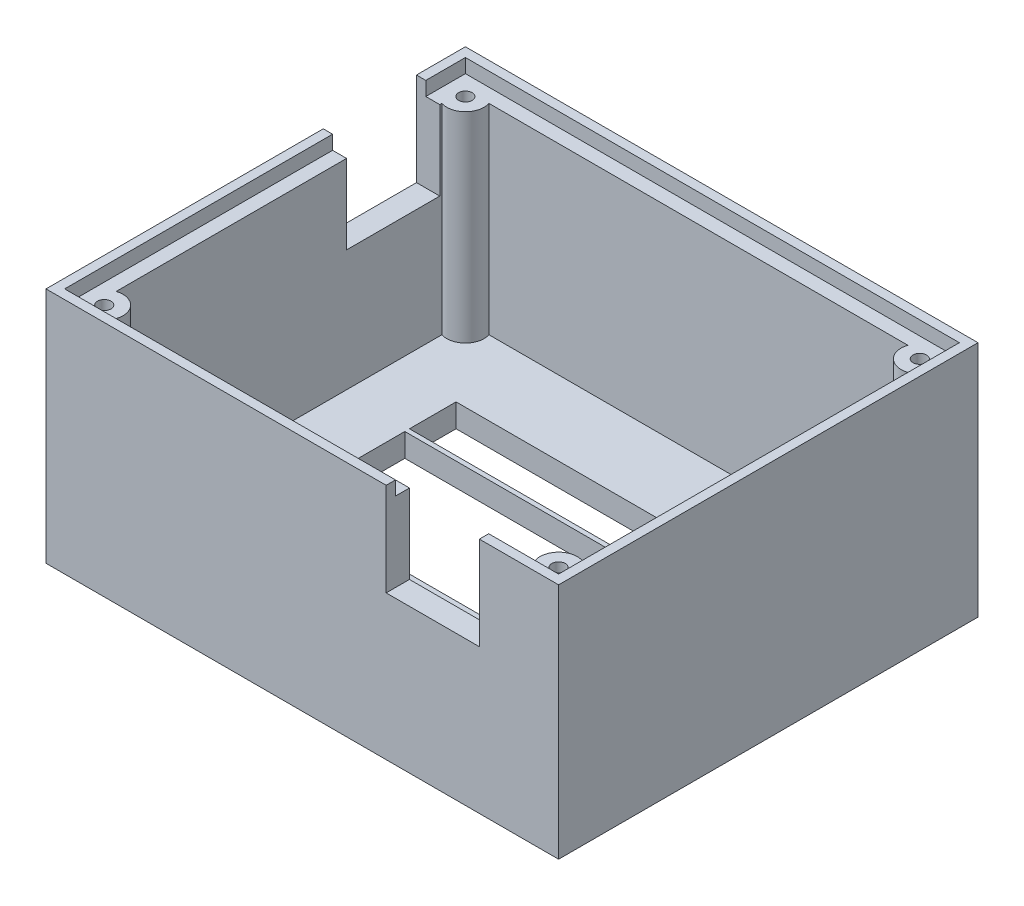
SolidWorks part; units mm, degrees
ref_plane "Front Plane" through (0, 0, 0) normal (0, 0, 1) x (1, 0, 0)
ref_plane "Top Plane" through (0, 0, 0) normal (0, 1, 0) x (1, 0, 0)
ref_plane "Right Plane" through (0, 0, 0) normal (1, 0, 0) x (0, 0, -1)
sketch "Sketch1" plane through (0, 0, 0) normal (0, 1, 0) x (1, 0, 0)
  line L1 (-55, -45) -> (55, -45)
  line L2 (-55, -45) -> (-55, 45)
  line L3 (-55, 45) -> (55, 45)
  line L4 (55, -45) -> (55, 45)
extrude "Boss-Extrude1" add sketch "Sketch1" along normal blind 51
sketch "Sketch2" plane through (0, 51, 0) normal (0, 1, 0) x (1, 0, 0)
  line L1 (-50, 40) -> (50, 40)
  line L2 (-50, 40) -> (-50, -40)
  line L3 (-50, -40) -> (50, -40)
  line L4 (50, 40) -> (50, -40)
extrude "Cut-Extrude1" cut sketch "Sketch2" against normal blind 46
sketch "Sketch3" plane through (0, 51, 0) normal (0, 1, 0) x (1, 0, 0)
  line L1 (-53, 43) -> (53, 43)
  line L2 (-53, 43) -> (-53, 40)
  line L3 (-53, 40) -> (53, 40)
  line L4 (53, 43) -> (53, 40)
extrude "Cut-Extrude2" cut sketch "Sketch3" against normal blind 3
sketch "Sketch5" plane through (0, 51, 0) normal (0, 1, 0) x (1, 0, 0)
  line L1 (53, 40) -> (50, 40)
  line L2 (53, 40) -> (53, -43)
  line L3 (53, -43) -> (50, -43)
  line L4 (50, 40) -> (50, -43)
extrude "Cut-Extrude3" cut sketch "Sketch5" against normal blind 3
sketch "Sketch6" plane through (0, 51, 0) normal (0, 1, 0) x (1, 0, 0)
  line L1 (50, -43) -> (-53, -43)
  line L2 (50, -43) -> (50, -40)
  line L3 (50, -40) -> (-53, -40)
  line L4 (-53, -43) -> (-53, -40)
extrude "Cut-Extrude4" cut sketch "Sketch6" against normal blind 3
sketch "Sketch7" plane through (0, 51, 0) normal (0, 1, 0) x (1, 0, 0)
  line L1 (-53, 40) -> (-50, 40)
  line L2 (-53, 40) -> (-53, -40)
  line L3 (-53, -40) -> (-50, -40)
  line L4 (-50, 40) -> (-50, -40)
extrude "Cut-Extrude5" cut sketch "Sketch7" against normal blind 3
sketch "Sketch9" plane through (0, 5, 0) normal (0, 1, 0) x (1, 0, 0)
  circle A0 centre (-48.75, 38.75) radius 4
extrude "Boss-Extrude2" add sketch "Sketch9" along normal blind 43 contours A0
sketch "Sketch10" plane through (0, 5, 0) normal (0, 1, 0) x (1, 0, 0)
  circle A0 centre (48.75, 38.75) radius 4
  circle A1 centre (48.75, -38.75) radius 4
  circle A2 centre (-48.75, -38.75) radius 4
extrude "Boss-Extrude3" add sketch "Sketch10" along normal blind 43
hole_wizard "M2.5 Clearance Hole1" positions "Sketch11" profile "Sketch12" hole size "M2.5" standard "ANSI Metric"
sketch "Sketch11" plane through (0, 48, 0) normal (0, 1, 0) x (1, 0, 0)
  point P0 (-48.75, 38.75)
  point P3 (48.75, 38.75)
  point P6 (48.75, -38.75)
  point P9 (-48.75, -38.75)
  point P12 (0, 0)
  point P13 (0, 0)
  point P14 (0, 0)
  point P15 (0, 0)
sketch "Sketch12" plane through (-48.75, 48, -38.75) normal (1, 0, 0) x (0, 0, 1)
  line L0 (0, 0) -> (0, 5.8712)
  line L1 (0, 5.8712) -> (1.45, 5)
  line L2 (1.45, 5) -> (1.45, 0)
  line L5 (1.45, 0) -> (0, 0)
  line L10 (0, 5.8712) -> (-1.45, 5) construction
  line L11 (0, -6.35) -> (0, 107.95) construction
  dimension "Hole Dia." = 2.9
  dimension "Hole Depth" = 5
  dimension "Drill Angle" = 118
sketch "Sketch14" plane through (-55, 0, 0) normal (-1, 0, 0) x (0, 0, 1)
  line L1 (-34.5, 51) -> (-14.5, 51)
  line L2 (-34.5, 51) -> (-34.5, 31)
  line L3 (-34.5, 31) -> (-14.5, 31)
  line L4 (-14.5, 51) -> (-14.5, 31)
  point P4 (0, 0)
  point P5 (0, 0)
  point P6 (0, 0)
  point P7 (0, 0)
extrude "Cut-Extrude6" cut sketch "Sketch14" against normal blind 5
sketch "Sketch15" plane through (0, 0, 45) normal (0, 0, 1) x (1, 0, 0)
  line L1 (38, 51) -> (18, 51)
  line L2 (38, 51) -> (38, 31)
  line L3 (38, 31) -> (18, 31)
  line L4 (18, 51) -> (18, 31)
  point P4 (0, 0)
  point P5 (0, 0)
  point P6 (0, 0)
  point P7 (0, 0)
  point P8 (0, 0)
  point P9 (0, 0)
  point P10 (0, 0)
  point P11 (0, 0)
  point P12 (0, 0)
extrude "Cut-Extrude7" cut sketch "Sketch15" against normal blind 5
sketch "Sketch16" plane through (0, 5, 0) normal (0, 1, 0) x (1, 0, 0)
  line L1 (36, 13) -> (-36, 13)
  line L2 (36, 13) -> (36, -13)
  line L3 (36, -13) -> (-36, -13)
  line L4 (-36, 13) -> (-36, -13)
extrude "Cut-Extrude8" cut sketch "Sketch16" against normal blind 5
sketch "Sketch17" plane through (0, 0, 0) normal (0, -1, 0) x (1, 0, 0)
  line L1 (-36, -14) -> (36, -14)
  line L2 (-36, -14) -> (-36, -24)
  line L3 (-36, -24) -> (36, -24)
  line L4 (36, -14) -> (36, -24)
extrude "Cut-Extrude9" cut sketch "Sketch17" against normal blind 5
hole_wizard "M6 Clearance Hole2" positions "Sketch20" profile "Sketch21" hole size "M6" standard "ANSI Metric" end condition through all
sketch "Sketch20" plane through (0, 0, 0) normal (0, -1, 0) x (-1, 0, 0)
  point P0 (45.7075, -9.8997)
sketch "Sketch21" plane through (-45.7075, 0, 9.8997) normal (1, 0, 0) x (0, 0, -1)
  line L0 (0, 0) -> (0, 51)
  line L1 (0, 51) -> (3.3, 51)
  line L2 (3.3, 51) -> (3.3, 0)
  line L5 (3.3, 0) -> (0, 0)
  line L11 (0, -6.35) -> (0, 107.95) construction
  dimension "Thru Hole Dia." = 6.6
  dimension "Thru Hole Depth" = 51
